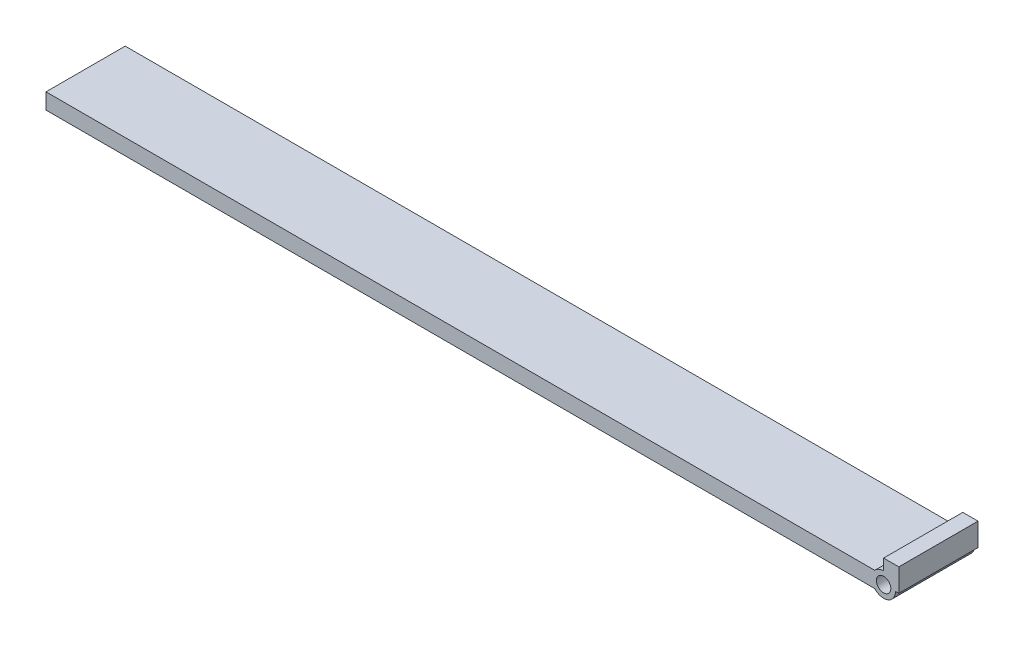
SolidWorks part; units mm, degrees
ref_plane "Front Plane" through (0, 0, 0) normal (0, 0, 1) x (1, 0, 0)
ref_plane "Top Plane" through (0, 0, 0) normal (0, 1, 0) x (1, 0, 0)
ref_plane "Right Plane" through (0, 0, 0) normal (1, 0, 0) x (0, 0, -1)
sketch "Sketch1" plane through (0, 0, 0) normal (0, 1, 0) x (1, 0, 0)
  line L1 (-264.4, -25) -> (264.4, -25)
  line L2 (-264.4, -25) -> (-264.4, 25)
  line L3 (-264.4, 25) -> (264.4, 25)
  line L4 (264.4, -25) -> (264.4, 25)
  line L5 (-264.4, -25) -> (264.4, 25) construction
  line L6 (-264.4, 25) -> (264.4, -25) construction
  point P0 (0, 0)
  dimension "D1" = 528.8
  dimension "D2" = 50
extrude "Extrude2" add sketch "Sketch1" along normal blind 10
sketch "Sketch2" plane through (0, 0, 25) normal (0, 0, 1) x (1, 0, 0)
  line L0 (264.4, 10) -> (264.4, 0) construction
  circle A0 centre (264.4, 5) radius 7.5
  dimension "D1" = 15
extrude "Extrude3" add sketch "Sketch2" against normal blind 50
sketch "Sketch3" plane through (0, 0, 25) normal (0, 0, 1) x (1, 0, 0)
  line L1 (264.4, 5) -> (273.9998, 5)
  line L2 (264.4, 5) -> (264.4, 19.4848)
  line L3 (264.4, 19.4848) -> (273.9998, 19.4848)
  line L4 (273.9998, 5) -> (273.9998, 19.4848)
extrude "Extrude4" add sketch "Sketch3" against normal blind 50
sketch "Sketch5" plane through (0, 0, 25) normal (0, 0, 1) x (1, 0, 0)
  circle A0 centre (264.4, 5) radius 4.5502
extrude "Extrude5" cut sketch "Sketch5" against normal blind 50
